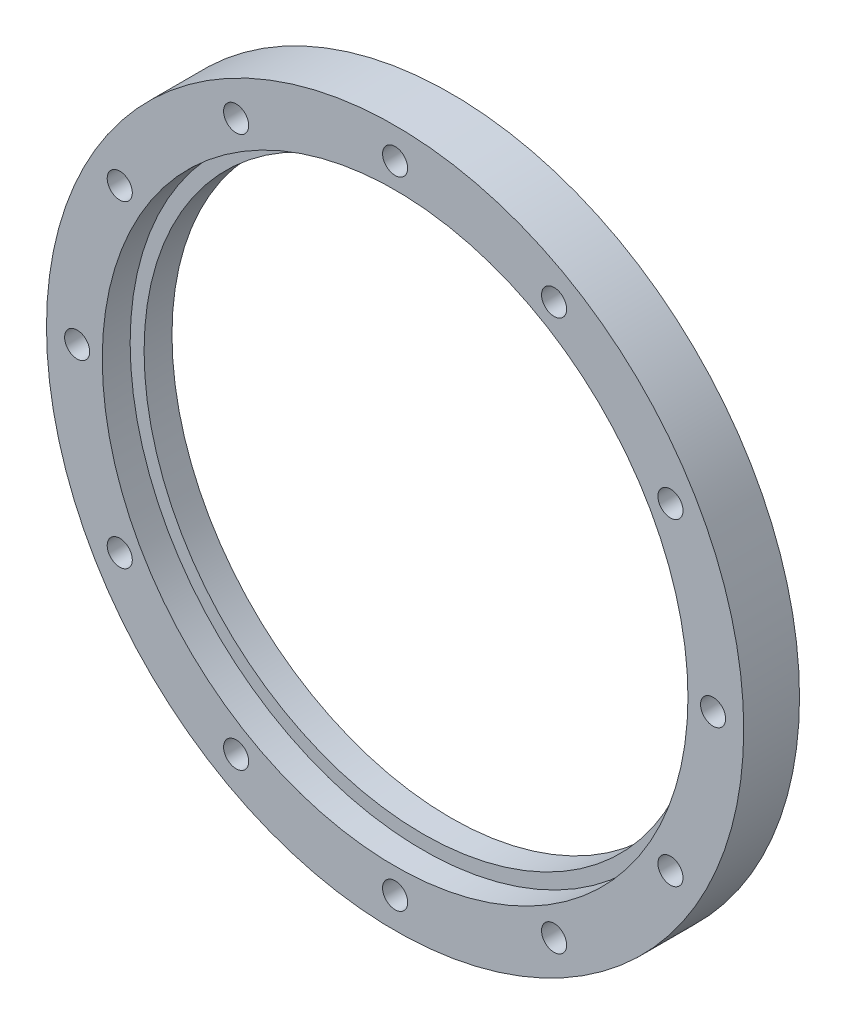
SolidWorks part; units mm, degrees
ref_plane "前视基准面" through (0, 0, 0) normal (0, 0, 1) x (1, 0, 0)
ref_plane "上视基准面" through (0, 0, 0) normal (0, 1, 0) x (1, 0, 0)
ref_plane "右视基准面" through (0, 0, 0) normal (1, 0, 0) x (0, 0, -1)
sketch "草图1" plane through (0, 0, 0) normal (0, 0, 1) x (1, 0, 0)
  circle A0 centre (0, 0) radius 62.5
  dimension "D1" = 125
extrude "凸台-拉伸1" add sketch "草图1" along normal blind 10
sketch "草图2" plane through (0, 0, 10) normal (0, 0, 1) x (1, 0, 0)
  circle A0 centre (0, 0) radius 50
  dimension "D1" = 100
extrude "切除-拉伸1" cut sketch "草图2" against normal through all contours A0
sketch "草图3" plane through (0, 0, 10) normal (0, 0, 1) x (1, 0, 0)
  circle A0 centre (0, 0) radius 52.5
  dimension "D1" = 105
extrude "切除-拉伸2" cut sketch "草图3" against normal blind 5
hole_wizard "打孔尺寸(%根据六角头螺)栓 全螺纹的类型9" positions "草图7" profile "草图6" counterbore size "M4" standard "GB" end condition through all
sketch "草图7" plane through (0, 0, 0) normal (0, 0, -1) x (-1, 0, 0)
  line L0 (0, 0) -> (0, 67.1144) construction
  circle A0 centre (0, 0) radius 57 construction
  point P0 (0, 57)
  dimension "D1" = 114
sketch "草图6" plane through (0, 57, 0) normal (1, 0, 0) x (0, 1, 0)
  line L0 (0, 0) -> (0, 10)
  line L1 (0, 10) -> (2.25, 10)
  line L3 (2.25, 10) -> (2.25, 3)
  line L4 (2.25, 3) -> (5, 3)
  line L5 (5, 3) -> (5, 0)
  line L7 (5, 0) -> (0, 0)
  line L11 (0, -6.35) -> (0, 107.95) construction
  dimension "通孔孔直径" = 4.5
  dimension "通孔孔深度" = 10
  dimension "柱形沉头孔直径" = 10
  dimension "柱形沉头孔深度" = 3
ref_axis "基准轴1" through (0, 0, 0) along (0, 0, 1)
pattern_circular "阵列(圆周)1" count 12 over 360 about axis through (0, 0, 0) along (0, 0, 1) of "打孔尺寸(%根据六角头螺)栓 全螺纹的类型9"
